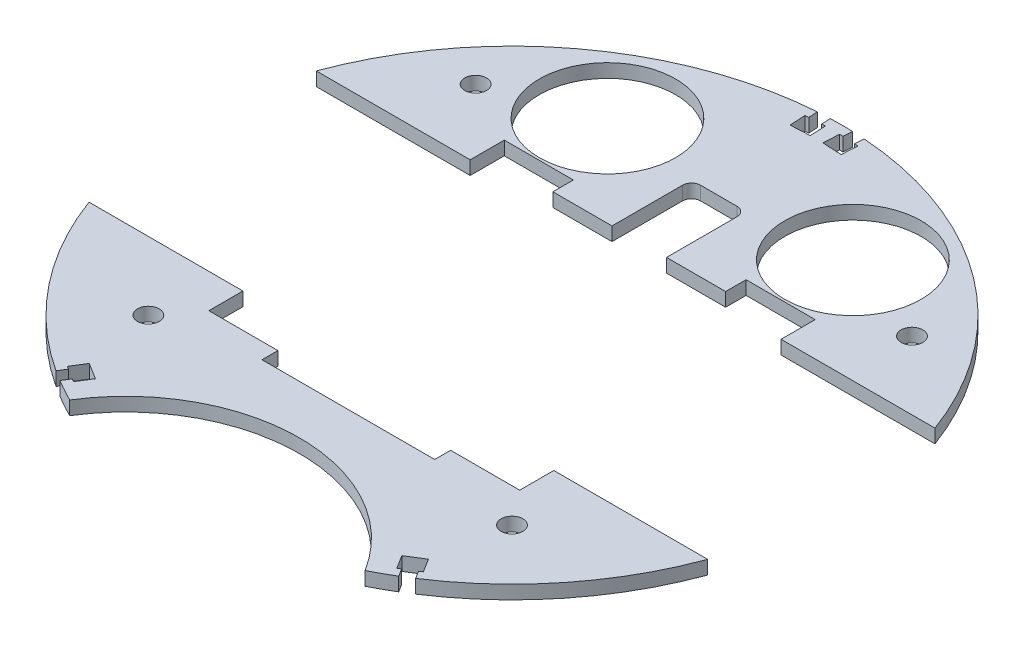
SolidWorks part; units mm, degrees
material "ABS"
ref_plane "Front Plane" through (0, 0, 0) normal (0, 0, 1) x (1, 0, 0)
ref_plane "Top Plane" through (0, 0, 0) normal (0, 1, 0) x (1, 0, 0)
ref_plane "Right Plane" through (0, 0, 0) normal (1, 0, 0) x (0, 0, -1)
sketch "Sketch1" plane through (0, 0, 0) normal (0, 1, 0) x (1, 0, 0)
  line L0 (0, -85) -> (-32.4891, -64.8129) construction
  line L1 (0, -85) -> (0, 0) construction
  arc A0 (32.4891, -64.8129) -> (-32.4891, -64.8129) centre (0, 0) ccw
  arc A1 (32.4891, -64.8129) -> (-32.4891, -64.8129) centre (0, -85) ccw
  dimension "D1" = 145
  dimension "D2" = 76.5
  dimension "D3" = 85
extrude "Boss-Extrude1" add sketch "Sketch1" along normal blind 3
sketch "solenoid placement" plane through (0, 3, 0) normal (0, 1, 0) x (1, 0, 0)
  line L4 (-19, -36) -> (19, -36)
  line L5 (-19, 28) -> (-19, -36)
  line L10 (19, 28) -> (-19, 28)
  line L11 (19, -36) -> (19, 28)
  line L12 (-19, -36) -> (19, -36)
  line L13 (-19, 28) -> (-19, -36)
  line L14 (19, 28) -> (-19, 28)
  line L15 (19, -36) -> (19, 28)
  dimension "D1" = 0
extrude "Cut-Extrude1" cut sketch "solenoid placement" against normal through all
sketch "Sketch7" plane through (0, 3, 0) normal (0, 1, 0) x (1, 0, 0)
  circle A3 centre (27, 48) radius 15
  circle A4 centre (27, 48) radius 15
  circle A5 centre (-27, 48) radius 15
  circle A6 centre (-27, 48) radius 15
  dimension "D1" = 0
  dimension "D2" = 0
extrude "Cut-Extrude6" cut sketch "Sketch7" against normal through all
sketch "Sketch8" plane through (0, 3, 0) normal (0, 1, 0) x (1, 0, 0)
  circle A1 centre (40, -40) radius 2.4
  circle A2 centre (40, -40) radius 2.4
  circle A3 centre (-40, -40) radius 2.4
  circle A4 centre (-40, -40) radius 2.4
  circle A5 centre (48, 40) radius 2.4
  circle A6 centre (48, 40) radius 2.4
  circle A7 centre (-48, 40) radius 2.4
  circle A8 centre (-48, 40) radius 2.4
  dimension "D1" = 0
  dimension "D2" = 0
  dimension "D3" = 0
  dimension "D4" = 0
extrude "Cut-Extrude7" cut sketch "Sketch8" against normal through all
sketch "Sketch3" plane through (0, 3, 0) normal (0, 1, 0) x (1, 0, 0)
  line L1 (-34.2, -32.5) -> (-22.2, -32.5)
  line L2 (-34.2, 25) -> (-68.0533, 25)
  line L3 (-34.2, 32.5) -> (-22.2, 32.5)
  line L4 (-22.2, -32.5) -> (-22.2, 32.5) construction
  line L8 (0, 0) -> (0, 72.5) construction
  line L17 (-34.2, -32.5) -> (-34.2, -25)
  line L18 (-34.2, -25) -> (-68.0533, -25)
  line L19 (-34.2, 25) -> (-34.2, 32.5)
  line L21 (-22.2, 32.5) -> (-19, 32.5)
  line L22 (-22.2, 32.5) -> (-22.2, -32.5) construction
  line L23 (-22.2, -32.5) -> (-19, -32.5)
  line L24 (-19, 32.5) -> (-19, -32.5)
  line L25 (22.2, 32.5) -> (22.2, -32.5) construction
  line L26 (22.2, -32.5) -> (22.2, 32.5) construction
  line L27 (19, 32.5) -> (19, -32.5)
  line L28 (22.2, -32.5) -> (19, -32.5)
  line L29 (22.2, 32.5) -> (19, 32.5)
  line L30 (34.2, 25) -> (34.2, 32.5)
  line L31 (34.2, -25) -> (68.0533, -25)
  line L32 (34.2, -32.5) -> (34.2, -25)
  line L33 (34.2, 32.5) -> (22.2, 32.5)
  line L34 (34.2, 25) -> (68.0533, 25)
  line L35 (34.2, -32.5) -> (22.2, -32.5)
  line L36 (-19, 28) -> (-19, -36) construction
  arc A0 (32.4891, -64.8129) -> (-32.4891, -64.8129) centre (0, 0) ccw construction
  arc A2 (68.0533, 25) -> (68.0533, -25) centre (0, 0) cw
  arc A3 (-68.0533, 25) -> (-68.0533, -25) centre (0, 0) ccw
  point P31 (-34.2, -32.5)
  dimension "D1" = 50
extrude "Cut-Extrude3" cut sketch "Sketch3" against normal through all
sketch "Sketch9" plane through (0, 3, 0) normal (0, 1, 0) x (1, 0, 0)
  line L0 (6, 43.5) -> (6, 28)
  line L1 (-6, 43.5) -> (-6, 28)
  line L2 (19, 28) -> (-19, 28) construction
  line L8 (-6, 28) -> (6, 28)
  line L10 (4, 45.5) -> (-4, 45.5)
  arc A0 (-6, 43.5) -> (-4, 45.5) centre (-4, 43.5) cw
  arc A1 (6, 43.5) -> (4, 45.5) centre (4, 43.5) ccw
  point P5 (0, 28)
  point P6 (0, 28)
  point P16 (-6, 45.5)
  point P19 (6, 45.5)
  dimension "D3" = 2
  dimension "D2" = 12
  dimension "D1" = 17.5
extrude "Cut-Extrude8" cut sketch "Sketch9" against normal through all
sketch "Sketch10" plane through (0, 3, 0) normal (0, 1, 0) x (1, 0, 0)
  line L0 (0, 0) -> (0, 72.5) construction
  line L1 (0, 0) -> (3.7944, 72.4006) construction
  line L2 (1.3844, 67.0194) -> (5.6286, 66.797)
  line L3 (1.3844, 67.0194) -> (1.5676, 70.5146)
  line L4 (5.6286, 66.797) -> (5.8118, 70.2922)
  line L5 (1.5676, 70.5146) -> (2.3415, 70.474)
  line L6 (2.3415, 70.474) -> (2.4462, 72.4713)
  line L7 (2.4462, 72.4713) -> (5.1425, 72.33)
  line L8 (5.1425, 72.33) -> (5.0378, 70.3327)
  line L9 (5.0378, 70.3327) -> (5.8118, 70.2922)
  line L10 (-5.0378, 70.3327) -> (-5.8118, 70.2922)
  line L11 (-5.1425, 72.33) -> (-5.0378, 70.3327)
  line L12 (-2.4462, 72.4713) -> (-5.1425, 72.33)
  line L13 (-2.3415, 70.474) -> (-2.4462, 72.4713)
  line L14 (-1.5676, 70.5146) -> (-2.3415, 70.474)
  line L15 (-5.6286, 66.797) -> (-5.8118, 70.2922)
  line L16 (-1.3844, 67.0194) -> (-1.5676, 70.5146)
  line L17 (-1.3844, 67.0194) -> (-5.6286, 66.797)
  line L18 (37.3067, -55.6931) -> (33.7025, -57.9453)
  line L19 (37.3067, -55.6931) -> (39.1614, -58.6613)
  line L20 (33.7025, -57.9453) -> (35.5572, -60.9135)
  line L21 (39.1614, -58.6613) -> (38.5042, -59.072)
  line L22 (38.5042, -59.072) -> (39.564, -60.7681)
  line L23 (39.564, -60.7681) -> (37.2743, -62.1989)
  line L24 (37.2743, -62.1989) -> (36.2144, -60.5028)
  line L25 (36.2144, -60.5028) -> (35.5572, -60.9135)
  line L26 (0, 0) -> (38.4191, -61.4835) construction
  line L27 (0, 0) -> (0, -85) construction
  line L28 (-33.7025, -57.9453) -> (-37.3067, -55.6931)
  line L29 (-33.7025, -57.9453) -> (-35.5572, -60.9135)
  line L30 (-37.3067, -55.6931) -> (-39.1614, -58.6613)
  line L31 (-35.5572, -60.9135) -> (-36.2144, -60.5028)
  line L32 (-36.2144, -60.5028) -> (-37.2743, -62.1989)
  line L33 (-37.2743, -62.1989) -> (-39.564, -60.7681)
  line L34 (-39.564, -60.7681) -> (-38.5042, -59.072)
  line L35 (-38.5042, -59.072) -> (-39.1614, -58.6613)
  line L36 (0, 0) -> (-38.4191, -61.4835) construction
  arc A1 (68.0533, 25) -> (-68.0533, 25) centre (0, 0) ccw construction
  point P1 (3.5065, 66.9082)
  point P15 (3.7944, 72.4006)
  point P36 (0, 0)
  point P49 (0, 0)
  dimension "D1" = 3.5
  dimension "D2" = 4.25
  dimension "D3" = 3
  dimension "D4" = 2.7
  dimension "D5" = 2
  dimension "D7" = 32
  dimension "D9" = 32
  dimension "D6" = 2
  dimension "D8" = 2
extrude "Cut-Extrude9" cut sketch "Sketch10" against normal through all
sketch "Sketch11" plane through (0, 3, 0) normal (0, 1, 0) x (1, 0, 0)
  line L4 (4, 48.5) -> (-4, 48.5)
  line L5 (7.1569, 48.5) -> (-7.1569, 48.5)
  line L10 (-8.4675, 63.6441) -> (-1.2274, 64.0235)
  line L11 (-8.8077, 70.1352) -> (-8.4675, 63.6441)
  line L12 (-6.4702, 63.7487) -> (-0.1047, 64.0823)
  line L13 (-8.6309, 66.7627) -> (-8.5721, 65.6413)
  line L17 (8.4675, 63.6441) -> (8.8077, 70.1352)
  line L18 (1.2274, 64.0235) -> (8.4675, 63.6441)
  line L19 (8.5721, 65.6413) -> (8.6309, 66.7627)
  line L20 (0.1047, 64.0823) -> (6.4702, 63.7487)
  arc A0 (-9.1412, 50.25) -> (-7.1569, 48.5) centre (-7.1569, 50.5) ccw
  arc A1 (9.1412, 50.25) -> (7.1569, 48.5) centre (7.1569, 50.5) cw
  arc A2 (18.004, 63.5907) -> (17.5082, 67.2585) centre (17.0044, 65.323) ccw
  arc A3 (10.9431, 68.6331) -> (8.6309, 66.7627) centre (10.6282, 66.658) ccw
  arc A4 (8.5721, 65.6413) -> (6.4702, 63.7487) centre (6.5749, 65.746) cw
  arc A5 (-0.1047, 64.0823) -> (0.1047, 64.0823) centre (0, 62.0851) cw
  arc A6 (-6.4702, 63.7487) -> (-8.5721, 65.6413) centre (-6.5749, 65.746) cw
  arc A7 (-10.9431, 68.6331) -> (-8.6309, 66.7627) centre (-10.6282, 66.658) cw
  arc A8 (-17.5082, 67.2585) -> (-18.004, 63.5907) centre (-17.0044, 65.323) ccw
  circle A9 centre (-27, 48) radius 18
  arc A10 (-9.1412, 50.25) -> (-18.004, 63.5907) centre (-27, 48) ccw
  circle A12 centre (27, 48) radius 18
  arc A13 (18.004, 63.5907) -> (9.1412, 50.25) centre (27, 48) ccw
  arc A15 (-4.9291, 69.325) -> (-65.2373, 23.9655) centre (0, 0) ccw
  arc A16 (-10.9431, 68.6331) -> (-17.5082, 67.2585) centre (0, 0) ccw
  arc A17 (17.5082, 67.2585) -> (10.9431, 68.6331) centre (0, 0) ccw
  dimension "D5" = 2
  dimension "D1" = 3
  dimension "D2" = 3
  dimension "D3" = 3
  dimension "D4" = 3
  dimension "D6" = 3
  dimension "D7" = 3
extrude "Cut-Extrude10" [suppressed] cut sketch "Sketch11" against normal through all
equation "\"smallPulleyTeeth\"= 15"
equation "\"largePulleyTeeth\"= 30"
equation "\"eighthThick\"= 3.0mm"
equation "\"sixteenthThick\" = 1.7mm"
equation "\"quarterThick\"=6.0mm"
equation "\"OD\" = 145mm"
equation "\"puckAngle\" = 60.5deg"
equation "\"D1@Sketch1\"=\"OD\""
equation "\"puckDiam\" = 76.5mm"
equation "\"D2@Sketch1\"=\"puckDiam\""
equation "\"D1@Boss-Extrude1\"=\"eighthThick\""
equation "\"axlePress\" = 5.9mm"
equation "\"press\" = 0.2mm"
equation "\"wheelClear\" = 0.3mm"
equation "\"10-32clear\" = 4.8mm"
equation "\"6-32clear\" = 3.3mm"
equation "\"8-32clear\" = 4.0mm"
equation "\"4-40clear\" = 3.0mm"
equation "\"wheelHeight\" = 22mm"
equation "\"wheelWell\" = 65mm"
equation "\"puckDist\" = 85mm"
equation "\"D3@Sketch1\"=\"puckDist\""
equation "\"scoopFillet\" = 5mm"
equation "\"10-32tap\" = 4.45mm"
equation "\"ledSmall\" = 3.1mm"
equation "\"ledLarge\" = 4.2mm"
equation "\"ledLength\" = 4.2mm"
equation "\"4-40close\" = 2.7mm"
equation "\"4-40nutThick\" = 2.2mm"
equation "\"4-40nutWidth\" = 6.2mm"
equation "\"4-40insertHeight\" = 3.5mm"
equation "\"4-40insert\" = 4.25mm"
equation "\"D1@Sketch10\"=\"4-40insertHeight\""
equation "\"D2@Sketch10\"=\"4-40insert\""
equation "\"D4@Sketch10\"=\"4-40close\""
